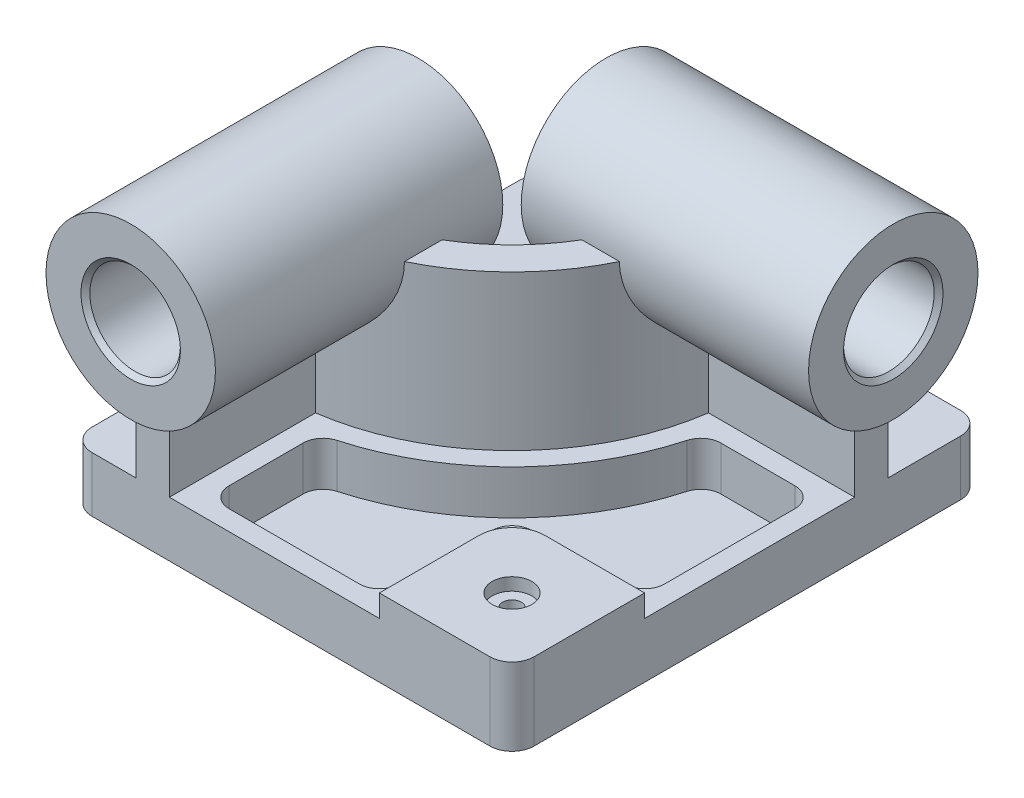
SolidWorks part; units mm, degrees
ref_plane "Front Plane" through (0, 0, 0) normal (0, 0, 1) x (1, 0, 0)
ref_plane "Top Plane" through (0, 0, 0) normal (0, 1, 0) x (1, 0, 0)
ref_plane "Right Plane" through (0, 0, 0) normal (1, 0, 0) x (0, 0, -1)
sketch "Sketch1" plane through (0, 0, 0) normal (0, 1, 0) x (1, 0, 0)
  line L0 (10, 0) -> (190, 0)
  line L1 (200, 10) -> (200, 203)
  line L2 (190, 213) -> (10, 213)
  line L3 (0, 203) -> (0, 10)
  arc A0 (190, 0) -> (200, 10) centre (190, 10) ccw
  arc A1 (10, 213) -> (0, 203) centre (10, 203) ccw
  arc A2 (10, 0) -> (0, 10) centre (10, 10) cw
  arc A3 (200, 203) -> (190, 213) centre (190, 203) ccw
  point P7 (200, 0)
  point P10 (0, 213)
  point P13 (0, 0)
  dimension "D3" = 10
  dimension "D1" = 213
  dimension "D2" = 200
extrude "Boss-Extrude1" add sketch "Sketch1" along normal blind 25
sketch "Sketch2" plane through (0, 25, 0) normal (0, 1, 0) x (1, 0, 0)
  line L1 (155, 60) -> (200, 60)
  line L2 (140, 45) -> (140, 0)
  line L3 (140, 0) -> (190, 0)
  line L4 (200, 60) -> (200, 10)
  line L5 (140, 60) -> (200, 0) construction
  line L6 (140, 0) -> (200, 60) construction
  arc A0 (155, 60) -> (140, 45) centre (155, 45) ccw
  arc A1 (190, 0) -> (200, 10) centre (190, 10) ccw
  point P0 (170, 30)
  dimension "D3" = 15
  dimension "D4" = 10
  dimension "D1" = 60
  dimension "D2" = 60
extrude "Boss-Extrude2" add sketch "Sketch2" along normal blind 35 from surface starting at face at (100, 0, -106.5)
sketch "Sketch7" plane through (0, 35, 0) normal (0, 1, 0) x (1, 0, 0)
  line L0 (140, 0) -> (200, 0)
  line L1 (170, 0) -> (170, 60)
  line L2 (200, 60) -> (155, 60) construction
  line L3 (140, 30) -> (200, 30)
  line L4 (200, 10) -> (200, 60) construction
  point P13 (170, 30)
  dimension "D1" = 60
hole_wizard "CBORE for M8 Hex Head Bolt2" positions "3DSketch3" profile "Sketch8" counterbore size "M8" standard "ANSI Metric" end condition through all
sketch3d "3DSketch3"
  point P0 (170, 35, -30)
sketch "Sketch8" plane through (170, 35, -30) normal (1, 0, 0) x (0, 0, 1)
  line L0 (0, 0) -> (0, 35)
  line L1 (0, 35) -> (4.2, 35)
  line L3 (4.2, 35) -> (4.2, 5.68)
  line L4 (4.2, 5.68) -> (9.005, 5.68)
  line L5 (9.005, 5.68) -> (9.005, 0)
  line L7 (9.005, 0) -> (0, 0)
  line L11 (0, -6.35) -> (0, 107.95) construction
  dimension "Thru Hole Dia." = 8.4
  dimension "Thru Hole Depth" = 35
  dimension "C'Bore Dia." = 18.01
  dimension "C'Bore Depth" = 5.68
sketch "Sketch9" plane through (0, 25, 0) normal (0, 1, 0) x (1, 0, 0)
  line L0 (182, 69) -> (140, 69)
  line L1 (131, 60) -> (131, 18)
  line L2 (122, 9) -> (63, 9)
  line L3 (54, 18) -> (54, 51.5095)
  line L4 (191, 78) -> (191, 137)
  line L5 (182, 146) -> (148.4905, 146)
  line L6 (140, 0) -> (140, 45) construction
  line L7 (10, 0) -> (140, 0) construction
  line L8 (155, 60) -> (200, 60) construction
  line L9 (200, 60) -> (200, 203) construction
  line L10 (200, 170) -> (120, 170)
  line L11 (200, 170) -> (30, 170) construction
  line L12 (30, 170) -> (30, 0) construction
  line L13 (140, 0) -> (190, 0) construction
  line L14 (200, 10) -> (200, 60) construction
  line L15 (30, 0) -> (30, 80)
  line L16 (200, 155) -> (133.923, 155)
  line L17 (45, 0) -> (45, 66.077)
  line L18 (45, 0) -> (45, 80) construction
  line L19 (45, 0) -> (30, 0)
  line L20 (200, 155) -> (200, 170)
  arc A0 (63, 9) -> (54, 18) centre (63, 18) cw
  arc A1 (131, 18) -> (122, 9) centre (122, 18) cw
  arc A2 (140, 69) -> (131, 60) centre (140, 60) ccw
  arc A3 (182, 69) -> (191, 78) centre (182, 78) ccw
  arc A4 (191, 137) -> (182, 146) centre (182, 137) ccw
  arc A5 (120, 170) -> (30, 80) centre (30, 170) cw
  arc A6 (139.8205, 139.4146) -> (60.5854, 60.1795) centre (30, 170) cw
  arc A7 (144, 170) -> (30, 56) centre (30, 170) cw construction
  arc A8 (139.8205, 139.4146) -> (148.4905, 146) centre (148.4905, 137) cw
  arc A9 (54, 51.5095) -> (60.5854, 60.1795) centre (63, 51.5095) cw
  arc A10 (133.923, 155) -> (45, 66.077) centre (30, 170) cw
  arc A11 (133.923, 155) -> (30, 65) centre (30, 170) cw construction
  line M27 (200, 60) -> (200, 203)
  line M33 (10, 0) -> (140, 0)
  dimension "D1" = 9
  dimension "D13" = 9
  dimension "D2" = 9
  dimension "D3" = 9
  dimension "D4" = 9
  dimension "D5" = 9
  dimension "D6" = 170
  dimension "D7" = 170
  dimension "D8" = 15
  dimension "D9" = 80
  dimension "D10" = 80
  dimension "D11" = 9
  dimension "D14" = 15
  dimension "D15" = 9
  dimension "D12" = 24
extrude "Cut-Extrude1" cut sketch "Sketch9" against normal blind 20 contours A9 L3 A0 L2 A1 L1 A2 L0 A3 L4 A4 L5 A8 A6 region at (126.7213, 25, -73.2787)
extrude "Boss-Extrude3" add sketch "Sketch9<3>" along normal blind 95 from surface contours A10 L16 L10 A5 L15 L17 M27 M33 region at (96.9024, 25, -103.0976) starting at face at (170, 0, -25.8)
sketch "Sketch9<3>" plane through (0, 25, 0) normal (0, 1, 0) x (1, 0, 0) same geometry as "Sketch9"
ref_plane "Plane1" through (200, 0, 0) normal (1, 0, 0) x (0, 0, -1)
sketch "Sketch10" plane through (200, 0, 0) normal (1, 0, 0) x (0, 0, -1)
  line L0 (155, 95) -> (170, 95) construction
  circle A0 centre (162.5, 95) radius 38.33
  circle A1 centre (162.5, 95) radius 20.5
  point P4 (162.5, 95)
  dimension "D1" = 41
  dimension "D2" = 76.66
extrude "Boss-Extrude4" add sketch "Sketch10" against normal blind 120
sketch "Sketch11" plane through (200, 0, 0) normal (1, 0, 0) x (0, 0, -1)
  line L0 (155, 95) -> (170, 95) construction
  line L1 (142, 95) -> (170, 95)
  line L2 (170, 95) -> (170, 75.9212)
  arc A0 (142, 95) -> (170, 75.9212) centre (162.5, 95) ccw
  arc A1 (170, 75.9212) -> (155, 75.9212) centre (162.5, 95) ccw construction
extrude "Cut-Extrude2" cut sketch "Sketch11" against normal blind 130
ref_plane "Plane2" through (0, 0, 0) normal (0, 0, 1) x (1, 0, 0)
sketch "Sketch12" plane through (0, 0, 0) normal (0, 0, 1) x (1, 0, 0)
  line L0 (30, 95) -> (45, 95) construction
  circle A0 centre (37.5, 95) radius 38.33
  circle A1 centre (37.5, 95) radius 20.5
  dimension "D1" = 76.66
  dimension "D2" = 41
extrude "Boss-Extrude5" add sketch "Sketch12" against normal blind 120 contours A0 A1 region at (0.2541, 95, 0)
sketch "Sketch13" plane through (0, 0, 0) normal (0, 0, 1) x (1, 0, 0)
  line L0 (30, 95) -> (45, 95) construction
  line L1 (25.688, 78.2451) -> (25.688, 100.1022)
  line L2 (25.688, 100.1022) -> (51.5722, 100.1022)
  line L3 (51.5722, 100.1022) -> (58, 95)
  arc A0 (58, 95) -> (25.688, 78.2451) centre (37.5, 95) cw
extrude "Cut-Extrude3" cut sketch "Sketch13" against normal blind 130
extrude "Boss-Extrude6" add sketch "Sketch10<2>" along normal blind 10
sketch "Sketch10<2>" plane through (200, 0, 0) normal (1, 0, 0) x (0, 0, -1) same geometry as "Sketch10"
extrude "Boss-Extrude7" add sketch "Sketch12<3>" along normal blind 10
sketch "Sketch12<3>" plane through (0, 0, 0) normal (0, 0, 1) x (1, 0, 0) same geometry as "Sketch12"
chamfer "Chamfer1" distance 2 angle 45 4 edges at (210, 95, -183) (58, 95, 10) (80, 95, -183) (58, 95, -120)
